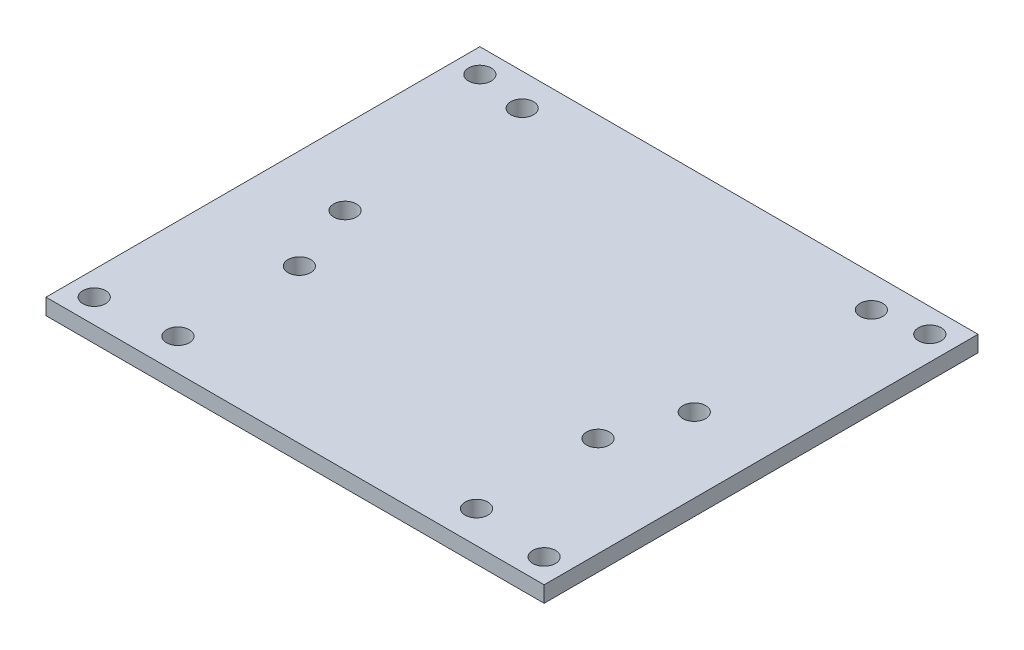
SolidWorks part; units mm, degrees
material "6061 Alloy"
ref_plane "Front Plane" through (0, 0, 0) normal (0, 0, 1) x (1, 0, 0)
ref_plane "Top Plane" through (0, 0, 0) normal (0, 1, 0) x (1, 0, 0)
ref_plane "Right Plane" through (0, 0, 0) normal (1, 0, 0) x (0, 0, -1)
sketch "Sketch1" plane through (0, 0, 0) normal (0, 1, 0) x (1, 0, 0)
  line L0 (-49.2125, 42.8625) -> (49.2125, 42.8625)
  line L1 (-44.45, -38.1) -> (44.45, -38.1) construction
  line L2 (-44.45, -38.1) -> (-44.45, 38.1) construction
  line L3 (-44.45, 38.1) -> (44.45, 38.1) construction
  line L4 (44.45, -38.1) -> (44.45, 38.1) construction
  line L5 (-44.45, -38.1) -> (44.45, 38.1) construction
  line L6 (-44.45, 38.1) -> (44.45, -38.1) construction
  line L7 (49.2125, -42.8625) -> (49.2125, 42.8625)
  line L8 (-49.2125, -42.8625) -> (49.2125, -42.8625)
  line L9 (-49.2125, -42.8625) -> (-49.2125, 42.8625)
  point P0 (0, 0)
  dimension "D1" = 88.9
  dimension "D2" = 76.2
  dimension "D3" = 4.7625
extrude "Boss-Extrude1" add sketch "Sketch1" along normal blind 3.175
hole_wizard "M3 Clearance Hole1" positions "3DSketch1" profile "Sketch2" hole size "M3" standard "ANSI Metric" end condition through all
sketch3d "3DSketch1"
  point P0 (-44.45, 0, 38.1)
  point P3 (44.45, 0, 38.1)
  point P6 (-44.45, 0, -38.1)
  point P9 (44.45, 0, -38.1)
sketch "Sketch2" plane through (-44.45, 0, 38.1) normal (1, 0, 0) x (0, 0, -1)
  line L0 (0, 0) -> (0, 3.175)
  line L1 (0, 3.175) -> (2.25, 3.175)
  line L2 (2.25, 3.175) -> (2.25, 0)
  line L5 (2.25, 0) -> (0, 0)
  line L11 (0, -6.35) -> (0, 107.95) construction
  dimension "Thru Hole Dia." = 4.5
  dimension "Thru Hole Depth" = 3.175
sketch "Sketch3" plane through (0, 3.175, 0) normal (0, 1, 0) x (1, 0, 0)
  line L0 (0, 19.0125) -> (0, -24.5125) construction
  line L1 (-34.5, 36.5125) -> (34.5, 36.5125) construction
  line L2 (-34.5, 36.5125) -> (-34.5, 1.5125) construction
  line L3 (-34.5, 1.5125) -> (34.5, 1.5125) construction
  line L4 (34.5, 36.5125) -> (34.5, 1.5125) construction
  line L5 (-34.5, 36.5125) -> (34.5, 1.5125) construction
  line L6 (-34.5, 1.5125) -> (34.5, 36.5125) construction
  line L7 (-29.5, -36.5125) -> (29.5, -36.5125) construction
  line L8 (-29.5, -36.5125) -> (-29.5, -12.5125) construction
  line L9 (-29.5, -12.5125) -> (29.5, -12.5125) construction
  line L10 (29.5, -36.5125) -> (29.5, -12.5125) construction
  line L11 (-29.5, -36.5125) -> (29.5, -12.5125) construction
  line L12 (-29.5, -12.5125) -> (29.5, -36.5125) construction
  line L13 (-49.2125, -42.8625) -> (49.2125, -42.8625) construction
  line L14 (49.2125, 42.8625) -> (-49.2125, 42.8625) construction
  point P0 (0, 19.0125)
  point P5 (0, -24.5125)
  dimension "D1" = 69
  dimension "D2" = 35
  dimension "D3" = 59
  dimension "D4" = 24
  dimension "D5" = 6.35
  dimension "D6" = 6.35
hole_wizard "M3 Clearance Hole2" positions "3DSketch2" profile "Sketch4" hole size "M3" standard "ANSI Metric" end condition through all
sketch3d "3DSketch2"
  point P0 (-29.5, 3.175, 36.5125)
  point P3 (-29.5, 3.175, 12.5125)
  point P6 (29.5, 3.175, 12.5125)
  point P9 (29.5, 3.175, 36.5125)
  point P12 (34.5, 3.175, -1.5125)
  point P15 (34.5, 3.175, -36.5125)
  point P18 (-34.5, 3.175, -36.5125)
  point P24 (-34.5, 3.175, -1.5125)
sketch "Sketch4" plane through (-29.5, 3.175, 36.5125) normal (1, 0, 0) x (0, 0, 1)
  line L0 (0, 0) -> (0, 3.175)
  line L1 (0, 3.175) -> (2.25, 3.175)
  line L2 (2.25, 3.175) -> (2.25, 0)
  line L5 (2.25, 0) -> (0, 0)
  line L11 (0, -6.35) -> (0, 107.95) construction
  dimension "Thru Hole Dia." = 4.5
  dimension "Thru Hole Depth" = 3.175
equation "\"D5@Sketch3\"=\"D6@Sketch3\""
